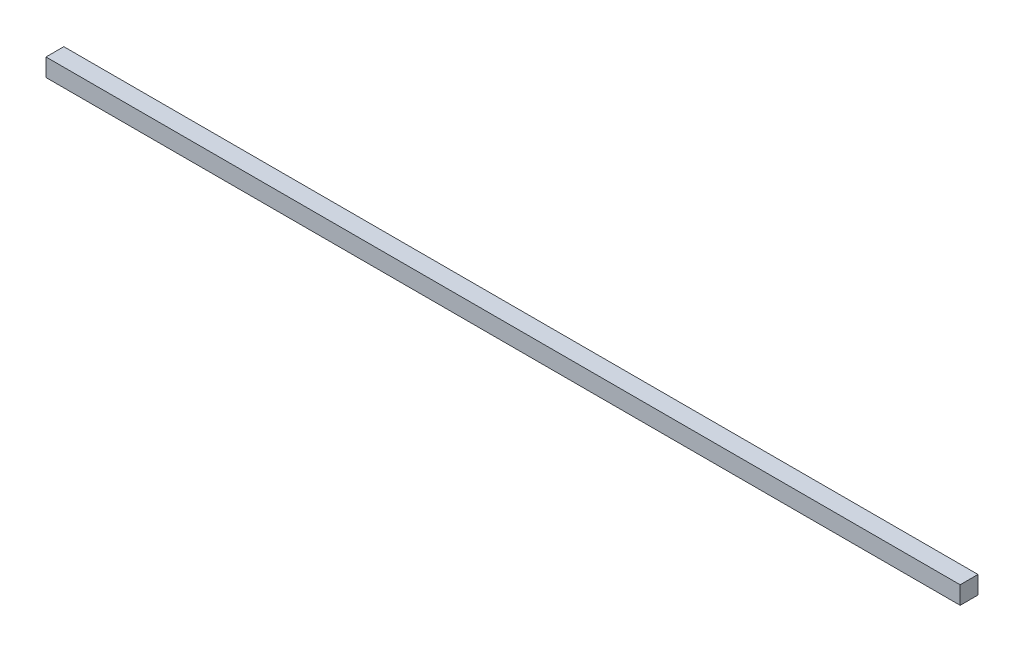
SolidWorks part; units mm, degrees
ref_plane "Спереди" through (0, 0, 0) normal (0, 0, 1) x (1, 0, 0)
ref_plane "Сверху" through (0, 0, 0) normal (0, 1, 0) x (1, 0, 0)
ref_plane "Справа" through (0, 0, 0) normal (1, 0, 0) x (0, 0, -1)
other "Configuration Table"
sketch "Эскиз1" plane through (0, 0, 0) normal (1, 0, 0) x (0, 0, -1)
  line L1 (0, 0) -> (6, 0)
  line L2 (0, 0) -> (0, 6)
  line L3 (0, 6) -> (6, 6)
  line L4 (6, 0) -> (6, 6)
extrude "Бобышка-Вытянуть1" add sketch "Эскиз1" along normal blind 307.5
